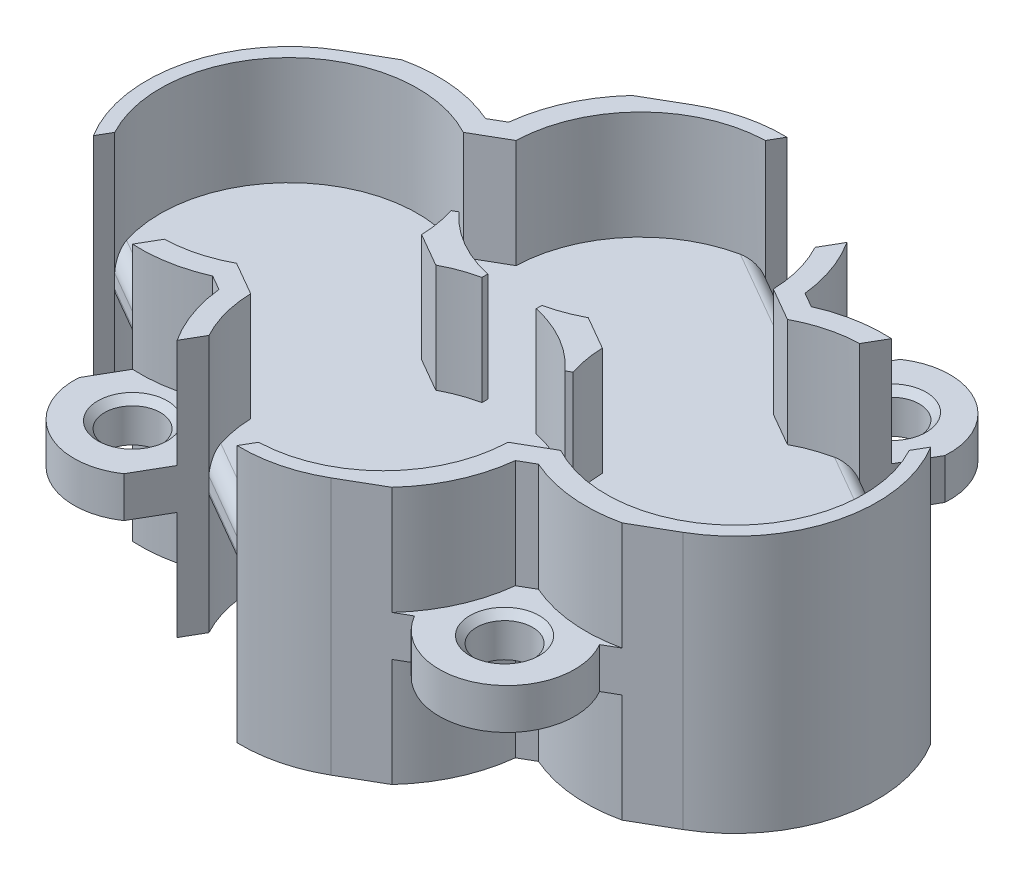
SolidWorks part; units mm, degrees
note: The reader was unsure of these and kept them because the rebuilt part matched: shared geometry of "Sketch1<4>", "Sketch1<6>".
ref_plane "Front Plane" through (0, 0, 0) normal (0, 0, 1) x (1, 0, 0)
ref_plane "Top Plane" through (0, 0, 0) normal (0, 1, 0) x (1, 0, 0)
ref_plane "Right Plane" through (0, 0, 0) normal (1, 0, 0) x (0, 0, -1)
sketch "Sketch1" plane through (0, 0, 0) normal (0, 1, 0) x (1, 0, 0)
  line L0 (-11.9589, 8.369) -> (-9.4955, 9.7913)
  line L1 (-6.9589, -0.2913) -> (-4.4955, 1.131)
  line L2 (-16.4545, 0) -> (0, 9.5) construction
  line L3 (-12.0193, 10.0662) -> (-10.9352, 10.6921)
  line L4 (0, 9.0625) -> (0, -9.0625) construction
  line L5 (-16.4545, 0) -> (16.4545, 0) construction
  line L6 (-5.25, 18.5933) -> (-21.7045, 9.0933)
  line L7 (5.25, -18.5933) -> (21.7045, -9.0933)
  line L8 (-21.7045, -9.0933) -> (-5.25, -18.5933)
  line L9 (5.25, 18.5933) -> (21.7045, 9.0933)
  line L10 (-12.0193, -10.0662) -> (-10.9352, -10.6921)
  line L11 (-16.4545, 0) -> (0, -9.5) construction
  line L12 (0, -19) -> (0, -20)
  line L13 (0, 20) -> (0, 19)
  line L14 (-11.9589, -8.369) -> (-9.4955, -9.7913)
  line L15 (0, 0) -> (-27.9836, 16.1563) construction
  circle A0 centre (-16.4545, 0) radius 9.5
  circle A1 centre (0, 9.5) radius 9.5
  circle A2 centre (16.4545, 0) radius 9.5
  circle A3 centre (0, -9.5) radius 9.5
  arc A4 (-21.7045, 9.0933) -> (-21.7045, -9.0933) centre (-16.4545, 0) ccw
  arc A5 (-5.25, -18.5933) -> (5.25, -18.5933) centre (0, -9.5) ccw
  arc A6 (21.7045, 9.0933) -> (21.7045, -9.0933) centre (16.4545, 0) cw
  arc A7 (-5.25, 18.5933) -> (5.25, 18.5933) centre (0, 9.5) cw
  arc A8 (-18.865, -10.7326) -> (-10.9999, -9.5523) centre (-16.4545, 0) ccw
  arc A9 (-8.0895, 16.9539) -> (-10.9999, 9.5523) centre (0, 9.5) ccw
  circle A12 centre (0, 9.5) radius 11 construction
  circle A13 centre (-16.4545, 0) radius 11 construction
  arc A15 (-10.9999, -9.5523) -> (-8.0895, -16.9539) centre (0, -9.5) ccw
  arc A19 (-10.9999, 9.5523) -> (-18.865, 10.7326) centre (-16.4545, 0) ccw
  dimension "D1" = 19
  dimension "D2" = 19
  dimension "D3" = 19
  dimension "D4" = 19
  dimension "D5" = 10.5
  dimension "D6" = 10.5
  dimension "D7" = 10.5
  dimension "D8" = 10.5
  dimension "D9" = 11
  dimension "D11" = 11
  dimension "D13" = 5
  dimension "D14" = 5
  dimension "D15" = 1.5
  dimension "D16" = 6.5
  dimension "D17" = 5
  dimension "D10" = 1.5
extrude "Boss-Extrude1" add sketch "Sketch1" against normal blind 3
extrude "Boss-Extrude2" add sketch "Sketch1<4>" against normal blind 3 contours A1 | A3
sketch "Sketch1<4>" plane through (0, 0, 0) normal (0, 1, 0) x (1, 0, 0) same geometry as "Sketch1"
extrude "Boss-Extrude3" add sketch "Sketch1<6>" along normal blind 8 and the other way offset from surface (11 mm away) 8
sketch "Sketch1<6>" plane through (0, 0, 0) normal (0, 1, 0) x (1, 0, 0) same geometry as "Sketch1"
sketch "Sketch3" plane through (0, 0, 0) normal (0, 1, 0) x (1, 0, 0)
  line L2 (-18.865, -10.7326) -> (-8.0895, -16.9539) construction
  line L3 (-8.0895, 16.9539) -> (-18.865, 10.7326) construction
  line L5 (-17.8074, -11.3433) -> (-9.1471, -16.3433)
  line L6 (-17.8074, 11.3433) -> (-9.1471, 16.3433)
  line L7 (-10.9999, -9.5523) -> (-12.1217, -11.4953) construction
  line L8 (-16.4545, 0) -> (0, -9.5) construction
  line L9 (-12.0193, -10.0662) -> (-10.9352, -10.6921) construction
  line L10 (-10.9999, 9.5523) -> (-11.9287, 11.1612) construction
  line L11 (-16.4545, 0) -> (0, 9.5) construction
  line L12 (-12.0193, 10.0662) -> (-10.9352, 10.6921) construction
  arc A0 (-17.8074, -11.3433) -> (-9.1471, -16.3433) centre (-13.4772, -13.8433) ccw
  arc A1 (-17.8074, 11.3433) -> (-9.1471, 16.3433) centre (-13.4772, 13.8433) cw
  dimension "D1" = 4
  dimension "D2" = 5
  dimension "D4" = 5
  dimension "D3" = 4
extrude "Boss-Extrude4" add sketch "Sketch3" against normal blind 3
sketch "Sketch4" plane through (0, 0, 0) normal (0, 1, 0) x (1, 0, 0)
  line L0 (-11.4772, -10.3792) -> (-13.7272, -14.2763)
  line L1 (-12.0193, -10.0662) -> (-10.9352, -10.6921) construction
  line L2 (-12.0193, -10.0662) -> (-10.9352, -10.6921) construction
  line L3 (-13.7272, 14.2763) -> (-11.4772, 10.3792)
  line L4 (-12.0193, 10.0662) -> (-10.9352, 10.6921) construction
  circle A0 centre (-13.7272, -14.2763) radius 2.0625
  circle A1 centre (-13.7272, 14.2763) radius 2.0625
  dimension "D1" = 4.125
  dimension "D3" = 4.125
  dimension "D2" = 4.5
  dimension "D4" = 4.5
extrude "Cut-Extrude1" cut sketch "Sketch4" against normal up to next
chamfer "Chamfer1" distance 0.5 angle 45 2 edges at (-13.7272, 0, 16.3388) (-13.7272, 0, -12.2138)
mirror "Mirror1" about plane through (0, 0, 0) normal (1, 0, 0) of "Chamfer1", "Cut-Extrude1", "Boss-Extrude3", "Boss-Extrude4"
sketch "Sketch5" plane through (0, 8, 0) normal (0, 1, 0) x (1, 0, 0)
  line L0 (-17.6743, 0) -> (16.6223, 0) construction
  line L1 (0, 0) -> (0, -9.5473) construction
  line L2 (-16.4545, 0) -> (0, -9.5) construction
  line L3 (-16.4545, 0) -> (-23.6771, -12.5099) construction
  line L4 (0, -9.5) -> (-7.4901, -22.4732) construction
  line L5 (-24.8235, -4.4955) -> (-16.1632, -9.4955)
  line L6 (-24.8235, -4.4955) -> (-27.1243, -8.4807)
  line L7 (-16.1632, -9.4955) -> (-18.4641, -13.4807)
  line L8 (-27.1243, -8.4807) -> (-18.4641, -13.4807)
  line L9 (-8.369, -13.9955) -> (0.2913, -18.9955)
  line L10 (-8.369, -13.9955) -> (-10.6699, -17.9807)
  line L11 (0.2913, -18.9955) -> (-2.0096, -22.9807)
  line L12 (-10.6699, -17.9807) -> (-2.0096, -22.9807)
  line L15 (16.4545, 0) -> (21.7045, 9.0933) construction
  line L16 (0, 9.5) -> (5.25, 18.5933) construction
  line L17 (-0.2913, 18.9955) -> (8.369, 13.9955)
  line L18 (-0.2913, 18.9955) -> (2.0096, 22.9807)
  line L19 (8.369, 13.9955) -> (10.6699, 17.9807)
  line L20 (2.0096, 22.9807) -> (10.6699, 17.9807)
  line L21 (16.1632, 9.4955) -> (24.8235, 4.4955)
  line L22 (16.1632, 9.4955) -> (18.4641, 13.4807)
  line L23 (24.8235, 4.4955) -> (27.1243, 8.4807)
  line L24 (18.4641, 13.4807) -> (27.1243, 8.4807)
  arc A0 (-11.9589, 8.369) -> (-11.9589, -8.369) centre (-16.4545, 0) ccw construction
  arc A1 (-9.4955, -9.7913) -> (9.4955, -9.7913) centre (0, -9.5) ccw construction
  arc A2 (11.9589, -8.369) -> (11.9589, 8.369) centre (16.4545, 0) ccw construction
  arc A3 (-17.8074, -11.3433) -> (-9.1471, -16.3433) centre (-13.4772, -13.8433) ccw construction
  arc A4 (-9.4955, -9.7913) -> (9.4955, -9.7913) centre (0, -9.5) ccw construction
  arc A5 (17.8074, 11.3433) -> (9.1471, 16.3433) centre (13.4772, 13.8433) ccw construction
  circle A7 centre (0, 9.5) radius 9.5 construction
  point P1 (-16.4545, 0)
  point P9 (0, -9.5)
  dimension "D1" = 10
  dimension "D3" = 5
  dimension "D4" = 5
  dimension "D5" = 10
  dimension "D8" = 10
  dimension "D9" = 5
  dimension "D11" = 10
  dimension "D12" = 5
extrude "Cut-Extrude2" cut sketch "Sketch5" against normal up to next
fillet "Fillet1" radius 1 8 edges at (-20.4934, 0, 6.9955) (-20.4934, -3, 6.9955) (-4.0389, 0, 16.4955) (-4.0389, -3, 16.4955) (4.0389, 0, -16.4955) (4.0389, -3, -16.4955) (20.4934, 0, -6.9955) (20.4934, -3, -6.9955)
sketch "Sketch6" plane through (0, 0, 0) normal (0, 1, 0) x (1, 0, 0)
  line L8 (-16.4545, 0) -> (0, 9.5) construction
  line L11 (-6.9589, 0.2913) -> (-4.4955, -1.131)
  line L12 (-16.4545, 0) -> (0, -9.5) construction
  line L13 (-7.0429, 3.1244) -> (-7.4116, 2.9115)
  line L14 (-2, 0.2129) -> (-2, -0.2129)
  line L15 (-16.4545, 0) -> (16.4545, 0) construction
  line L16 (4.4955, 1.131) -> (6.9589, -0.2913)
  line L17 (0, 9.5) -> (16.4545, 0) construction
  line L18 (173205.0808, -100000) -> (-173233.0643, 100016.1563) construction
  line L19 (2, 0.2129) -> (2, -0.2129)
  line L20 (7.4116, -2.9115) -> (7.0429, -3.1244)
  arc A2 (-8.2272, 4.75) -> (0, 0) centre (0, 9.5) ccw
  circle A16 centre (0, 9.5) radius 9.5 construction
  circle A24 centre (-16.4545, 0) radius 9.5 construction
  circle A25 centre (0, -9.5) radius 9.5 construction
  arc A26 (-6.9589, 0.2913) -> (-8.2272, 4.75) centre (-16.4545, 0) ccw
  arc A27 (0, 0) -> (-4.4955, -1.131) centre (0, -9.5) ccw
  circle A28 centre (16.4545, 0) radius 9.5 construction
  arc A29 (4.4955, 1.131) -> (0, 0) centre (0, 9.5) cw
  arc A30 (8.2272, -4.75) -> (6.9589, -0.2913) centre (16.4545, 0) cw
  arc A31 (8.2272, -4.75) -> (0, 0) centre (0, -9.5) ccw
  dimension "D1" = 5
  dimension "D2" = 2
  dimension "D3" = 2
  dimension "D4" = 10
  dimension "D5" = 2
  dimension "D6" = 2
extrude "Boss-Extrude5" add sketch "Sketch6" along normal blind 8 and the other way offset from surface (11 mm away) 8 contours A27 L14 A2 L13 A26 L11 | A31 L20 A30 L16 A29 L19 other way up to face at (13.7272, -3, 16.3388)
equation "\"D2@Sketch1\"=\"D1@Sketch1\""
equation "\"D3@Sketch1\"=\"D1@Sketch1\""
equation "\"D4@Sketch1\"=\"D1@Sketch1\""
